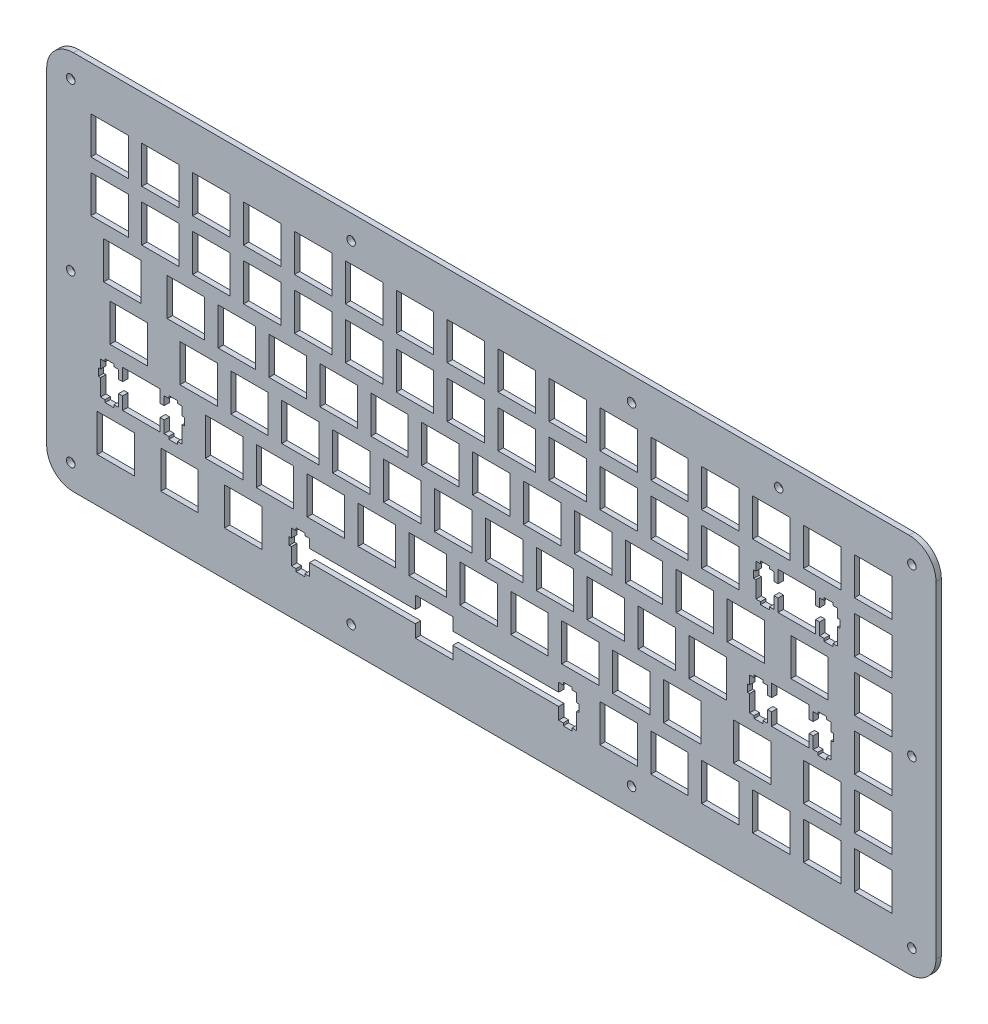
SolidWorks part; units mm, degrees
ref_plane "前视基准面" through (0, 0, 0) normal (0, 0, 1) x (1, 0, 0)
ref_plane "上视基准面" through (0, 0, 0) normal (0, 1, 0) x (1, 0, 0)
ref_plane "右视基准面" through (0, 0, 0) normal (1, 0, 0) x (0, 0, -1)
sketch "草图1" plane through (0, 0, 0) normal (0, 0, 1) x (1, 0, 0)
  line L0 (-71.9647, 54.2413) -> (-57.9647, 54.2413)
  line L1 (-172.8986, 61.7663) -> (147.9033, 61.7663) construction
  line L2 (-172.8986, 61.7663) -> (-172.8986, -68.5358) construction
  line L3 (-172.8986, -68.5358) -> (147.9033, -68.5358) construction
  line L4 (147.9033, 61.7663) -> (147.9033, -68.5358) construction
  line L5 (-165.3745, 54.2413) -> (140.3763, 54.2413) construction
  line L6 (-165.3745, 54.2413) -> (-165.3745, -61.009) construction
  line L7 (-165.3745, -61.009) -> (140.3763, -61.009) construction
  line L8 (140.3763, 54.2413) -> (140.3763, -61.009) construction
  line L9 (32.9683, 54.2413) -> (46.9683, 54.2413)
  line L10 (-165.3745, 3.6152) -> (-165.3745, -10.3848)
  line L11 (-71.9647, -61.009) -> (-57.9647, -61.009)
  line L12 (32.9683, -61.009) -> (46.9683, -61.009)
  line L13 (140.3763, 3.6152) -> (140.3763, -10.3848)
  line L14 (135.9033, 59.7663) -> (135.9033, 56.2413)
  line L15 (142.3763, 49.7663) -> (145.9033, 49.7663)
  line L16 (142.3763, -56.5358) -> (145.9033, -56.5358)
  line L17 (135.9033, -63.009) -> (135.9033, -66.5358)
  line L18 (-160.8986, -63.009) -> (-160.8986, -66.5358)
  line L19 (-167.3745, -56.5358) -> (-170.8986, -56.5358)
  line L20 (-160.8986, 56.2413) -> (-160.8986, 59.7663)
  line L21 (-167.3745, 49.7663) -> (-170.8986, 49.7663)
  line L22 (-73.9647, 56.2413) -> (-73.9647, 59.7663)
  line L23 (-55.9647, 56.2413) -> (-55.9647, 59.7663)
  line L24 (30.9683, 56.2413) -> (30.9683, 59.7663)
  line L25 (48.9683, 56.2413) -> (48.9683, 59.7663)
  line L26 (142.3763, 5.6152) -> (145.9033, 5.6152)
  line L27 (142.3763, -12.3848) -> (145.9033, -12.3848)
  line L28 (48.9683, -63.009) -> (48.9683, -66.5358)
  line L29 (30.9683, -63.009) -> (30.9683, -66.5358)
  line L30 (-55.9647, -63.009) -> (-55.9647, -66.5358)
  line L31 (-73.9647, -63.009) -> (-73.9647, -66.5358)
  line L32 (-167.3745, 5.6152) -> (-170.8986, 5.6152)
  line L33 (-167.3745, -12.3848) -> (-170.8986, -12.3848)
  line L34 (-158.8986, 61.7663) -> (-75.9647, 61.7663)
  line L35 (-53.9647, 61.7663) -> (28.9683, 61.7663)
  line L36 (147.9033, 47.7663) -> (147.9033, 7.6152)
  line L37 (147.9033, -14.3848) -> (147.9033, -54.5358)
  line L38 (133.9033, -68.5358) -> (50.9683, -68.5358)
  line L39 (28.9683, -68.5358) -> (-53.9647, -68.5358)
  line L40 (-75.9647, -68.5358) -> (-158.8986, -68.5358)
  line L41 (-172.8986, -54.5358) -> (-172.8986, -14.3848)
  line L42 (-172.8986, 7.6152) -> (-172.8986, 47.7663)
  line L43 (-165.3745, 51.7663) -> (-165.3745, 52.2413)
  line L44 (-163.3745, 54.2413) -> (-162.8986, 54.2413)
  line L45 (137.9033, 54.2413) -> (138.3763, 54.2413)
  line L46 (140.3763, 52.2413) -> (140.3763, 51.7663)
  line L47 (140.3763, -58.5358) -> (140.3763, -59.009)
  line L48 (138.3763, -61.009) -> (137.9033, -61.009)
  line L49 (-165.3745, -58.5358) -> (-165.3745, -59.009)
  line L50 (-163.3745, -61.009) -> (-162.8986, -61.009)
  line L51 (88.0363, 54.2413) -> (102.0363, 54.2413)
  line L52 (104.0363, 56.2413) -> (104.0363, 59.7663)
  line L53 (106.0363, 61.7663) -> (133.9033, 61.7663)
  line L54 (86.0363, 56.2413) -> (86.0363, 59.7663)
  line L55 (84.0363, 61.7663) -> (50.9683, 61.7663)
  line L56 (-168.8986, 67.7663) -> (143.9033, 67.7663)
  line L57 (153.9033, 57.7663) -> (153.9033, -64.5358)
  line L58 (143.9033, -74.5358) -> (-168.8986, -74.5358)
  line L59 (-178.8986, 57.7663) -> (-178.8986, -64.5358)
  line L60 (-40.9307, -44.0081) -> (-40.9307, -48.71)
  line L61 (-40.9307, -48.71) -> (-80.555, -48.71)
  line L62 (-80.555, -48.71) -> (-80.555, -45.4784)
  line L63 (-80.555, -45.4784) -> (-82.2801, -45.4784)
  line L64 (-82.2801, -45.4784) -> (-82.2801, -44.5579)
  line L65 (-82.2801, -44.5579) -> (-85.5807, -44.5579)
  line L66 (-85.5807, -44.5579) -> (-85.5807, -45.4784)
  line L67 (-85.5807, -45.4784) -> (-87.3047, -45.4784)
  line L68 (-87.3047, -45.4784) -> (-87.3047, -48.71)
  line L69 (-87.3047, -48.71) -> (-88.1298, -48.71)
  line L70 (-88.1298, -48.71) -> (-88.1298, -51.5088)
  line L71 (-88.1298, -51.5088) -> (-87.3047, -51.5088)
  line L72 (-87.3047, -51.5088) -> (-87.3047, -57.7788)
  line L73 (-87.3047, -57.7788) -> (-85.5807, -57.7788)
  line L74 (-85.5807, -57.7788) -> (-85.5807, -58.7587)
  line L75 (-85.5807, -58.7587) -> (-82.2801, -58.7587)
  line L76 (-82.2801, -58.7587) -> (-82.2801, -57.7788)
  line L77 (-82.2801, -57.7788) -> (-80.555, -57.7788)
  line L78 (-80.555, -57.7788) -> (-80.555, -53.3084)
  line L79 (-80.555, -53.3084) -> (-40.9307, -53.3084)
  line L80 (-40.9307, -53.3084) -> (-40.9307, -58.009)
  line L81 (-40.9307, -58.009) -> (-26.9297, -58.009)
  line L82 (-26.9297, -58.009) -> (-26.9297, -53.3084)
  line L83 (-26.9297, -53.3084) -> (12.6943, -53.3084)
  line L84 (12.6943, -53.3084) -> (12.6943, -57.7788)
  line L85 (12.6943, -57.7788) -> (14.4193, -57.7788)
  line L86 (14.4193, -57.7788) -> (14.4193, -58.7587)
  line L87 (14.4193, -58.7587) -> (17.7193, -58.7587)
  line L88 (17.7193, -58.7587) -> (17.7193, -57.7788)
  line L89 (17.7193, -57.7788) -> (19.4453, -57.7788)
  line L90 (19.4453, -57.7788) -> (19.4453, -51.5088)
  line L91 (19.4453, -51.5088) -> (20.2693, -51.5088)
  line L92 (20.2693, -51.5088) -> (20.2693, -48.71)
  line L93 (20.2693, -48.71) -> (19.4453, -48.71)
  line L94 (19.4453, -48.71) -> (19.4453, -45.4784)
  line L95 (19.4453, -45.4784) -> (17.7193, -45.4784)
  line L96 (17.7193, -45.4784) -> (17.7193, -44.5579)
  line L97 (17.7193, -44.5579) -> (14.4193, -44.5579)
  line L98 (14.4193, -44.5579) -> (14.4193, -45.4784)
  line L99 (14.4193, -45.4784) -> (12.6943, -45.4784)
  line L100 (12.6943, -45.4784) -> (12.6943, -48.71)
  line L101 (12.6943, -48.71) -> (-26.9297, -48.71)
  line L102 (-26.9297, -48.71) -> (-26.9297, -44.0081)
  line L103 (-26.9297, -44.0081) -> (-40.9307, -44.0081)
  line L104 (123.3763, -44.0081) -> (137.3763, -44.0081)
  line L105 (137.3763, -44.0081) -> (137.3763, -58.009)
  line L106 (137.3763, -58.009) -> (123.3763, -58.009)
  line L107 (123.3763, -58.009) -> (123.3763, -44.0081)
  line L108 (104.3263, -44.0081) -> (118.3263, -44.0081)
  line L109 (118.3263, -44.0081) -> (118.3263, -58.009)
  line L110 (118.3263, -58.009) -> (104.3263, -58.009)
  line L111 (104.3263, -58.009) -> (104.3263, -44.0081)
  line L112 (85.2763, -44.0081) -> (99.2763, -44.0081)
  line L113 (99.2763, -44.0081) -> (99.2763, -58.009)
  line L114 (99.2763, -58.009) -> (85.2763, -58.009)
  line L115 (85.2763, -58.009) -> (85.2763, -44.0081)
  line L116 (66.2263, -44.0081) -> (80.2263, -44.0081)
  line L117 (80.2263, -44.0081) -> (80.2263, -58.009)
  line L118 (80.2263, -58.009) -> (66.2263, -58.009)
  line L119 (66.2263, -58.009) -> (66.2263, -44.0081)
  line L120 (47.1763, -44.0081) -> (61.1763, -44.0081)
  line L121 (61.1763, -44.0081) -> (61.1763, -58.009)
  line L122 (61.1763, -58.009) -> (47.1763, -58.009)
  line L123 (47.1763, -58.009) -> (47.1763, -44.0081)
  line L124 (28.1263, -44.0081) -> (42.1263, -44.0081)
  line L125 (42.1263, -44.0081) -> (42.1263, -58.009)
  line L126 (42.1263, -58.009) -> (28.1263, -58.009)
  line L127 (28.1263, -58.009) -> (28.1263, -44.0081)
  line L128 (-112.3671, -44.0081) -> (-98.3674, -44.0081)
  line L129 (-98.3674, -44.0081) -> (-98.3674, -58.009)
  line L130 (-98.3674, -58.009) -> (-112.3671, -58.009)
  line L131 (-112.3671, -58.009) -> (-112.3671, -44.0081)
  line L132 (-136.1806, -44.0081) -> (-122.1799, -44.0081)
  line L133 (-122.1799, -44.0081) -> (-122.1799, -58.009)
  line L134 (-122.1799, -58.009) -> (-136.1806, -58.009)
  line L135 (-136.1806, -58.009) -> (-136.1806, -44.0081)
  line L136 (-159.9919, -44.0081) -> (-145.9924, -44.0081)
  line L137 (-145.9924, -44.0081) -> (-145.9924, -58.009)
  line L138 (-145.9924, -58.009) -> (-159.9919, -58.009)
  line L139 (-159.9919, -58.009) -> (-159.9919, -44.0081)
  line L140 (-150.4669, -24.9593) -> (-150.4669, -29.6601)
  line L141 (-150.4669, -29.6601) -> (-151.9924, -29.6601)
  line L142 (-151.9924, -29.6601) -> (-151.9924, -26.4297)
  line L143 (-151.9924, -26.4297) -> (-153.7177, -26.4297)
  line L144 (-153.7177, -26.4297) -> (-153.7177, -25.5079)
  line L145 (-153.7177, -25.5079) -> (-157.0167, -25.5079)
  line L146 (-157.0167, -25.5079) -> (-157.0167, -26.4297)
  line L147 (-157.0167, -26.4297) -> (-158.742, -26.4297)
  line L148 (-158.742, -26.4297) -> (-158.742, -29.6601)
  line L149 (-158.742, -29.6601) -> (-159.5675, -29.6601)
  line L150 (-159.5675, -29.6601) -> (-159.5675, -32.4586)
  line L151 (-159.5675, -32.4586) -> (-158.742, -32.4586)
  line L152 (-158.742, -32.4586) -> (-158.742, -38.7288)
  line L153 (-158.742, -38.7288) -> (-157.0167, -38.7288)
  line L154 (-157.0167, -38.7288) -> (-157.0167, -39.71)
  line L155 (-157.0167, -39.71) -> (-153.7177, -39.71)
  line L156 (-153.7177, -39.71) -> (-153.7177, -38.7288)
  line L157 (-153.7177, -38.7288) -> (-151.9924, -38.7288)
  line L158 (-151.9924, -38.7288) -> (-151.9924, -34.2584)
  line L159 (-151.9924, -34.2584) -> (-150.4669, -34.2584)
  line L160 (-150.4669, -34.2584) -> (-150.4669, -38.959)
  line L161 (-150.4669, -38.959) -> (-136.4674, -38.959)
  line L162 (-136.4674, -38.959) -> (-136.4674, -34.2584)
  line L163 (-136.4674, -34.2584) -> (-134.942, -34.2584)
  line L164 (-134.942, -34.2584) -> (-134.942, -38.7288)
  line L165 (-134.942, -38.7288) -> (-133.2166, -38.7288)
  line L166 (-133.2166, -38.7288) -> (-133.2166, -39.71)
  line L167 (-133.2166, -39.71) -> (-129.9178, -39.71)
  line L168 (-129.9178, -39.71) -> (-129.9178, -38.7288)
  line L169 (-129.9178, -38.7288) -> (-128.1923, -38.7288)
  line L170 (-128.1923, -38.7288) -> (-128.1923, -32.4586)
  line L171 (-128.1923, -32.4586) -> (-127.3668, -32.4586)
  line L172 (-127.3668, -32.4586) -> (-127.3668, -29.6601)
  line L173 (-127.3668, -29.6601) -> (-128.1923, -29.6601)
  line L174 (-128.1923, -29.6601) -> (-128.1923, -26.4297)
  line L175 (-128.1923, -26.4297) -> (-129.9178, -26.4297)
  line L176 (-129.9178, -26.4297) -> (-129.9178, -25.5079)
  line L177 (-129.9178, -25.5079) -> (-133.2166, -25.5079)
  line L178 (-133.2166, -25.5079) -> (-133.2166, -26.4297)
  line L179 (-133.2166, -26.4297) -> (-134.942, -26.4297)
  line L180 (-134.942, -26.4297) -> (-134.942, -29.6601)
  line L181 (-134.942, -29.6601) -> (-136.4674, -29.6601)
  line L182 (-136.4674, -29.6601) -> (-136.4674, -24.9593)
  line L183 (-136.4674, -24.9593) -> (-150.4669, -24.9593)
  line L184 (123.3763, -24.9593) -> (137.3763, -24.9593)
  line L185 (137.3763, -24.9593) -> (137.3763, -38.959)
  line L186 (137.3763, -38.959) -> (123.3763, -38.959)
  line L187 (123.3763, -38.959) -> (123.3763, -24.9593)
  line L188 (104.3263, -24.9593) -> (118.3263, -24.9593)
  line L189 (118.3263, -24.9593) -> (118.3263, -38.959)
  line L190 (118.3263, -38.959) -> (104.3263, -38.959)
  line L191 (104.3263, -38.959) -> (104.3263, -24.9593)
  line L192 (78.1333, -24.9593) -> (92.1323, -24.9593)
  line L193 (92.1323, -24.9593) -> (92.1323, -38.959)
  line L194 (92.1323, -38.959) -> (78.1333, -38.959)
  line L195 (78.1333, -38.959) -> (78.1333, -24.9593)
  line L196 (51.9393, -24.9593) -> (65.9393, -24.9593)
  line L197 (65.9393, -24.9593) -> (65.9393, -38.959)
  line L198 (65.9393, -38.959) -> (51.9393, -38.959)
  line L199 (51.9393, -38.959) -> (51.9393, -24.9593)
  line L200 (32.8893, -24.9593) -> (46.8893, -24.9593)
  line L201 (46.8893, -24.9593) -> (46.8893, -38.959)
  line L202 (46.8893, -38.959) -> (32.8893, -38.959)
  line L203 (32.8893, -38.959) -> (32.8893, -24.9593)
  line L204 (13.8393, -24.9593) -> (27.8393, -24.9593)
  line L205 (27.8393, -24.9593) -> (27.8393, -38.959)
  line L206 (27.8393, -38.959) -> (13.8393, -38.959)
  line L207 (13.8393, -38.959) -> (13.8393, -24.9593)
  line L208 (-5.2107, -24.9593) -> (8.7893, -24.9593)
  line L209 (8.7893, -24.9593) -> (8.7893, -38.959)
  line L210 (8.7893, -38.959) -> (-5.2107, -38.959)
  line L211 (-5.2107, -38.959) -> (-5.2107, -24.9593)
  line L212 (-24.2607, -24.9593) -> (-10.2607, -24.9593)
  line L213 (-10.2607, -24.9593) -> (-10.2607, -38.959)
  line L214 (-10.2607, -38.959) -> (-24.2607, -38.959)
  line L215 (-24.2607, -38.959) -> (-24.2607, -24.9593)
  line L216 (-43.3107, -24.9593) -> (-29.3107, -24.9593)
  line L217 (-29.3107, -24.9593) -> (-29.3107, -38.959)
  line L218 (-29.3107, -38.959) -> (-43.3107, -38.959)
  line L219 (-43.3107, -38.959) -> (-43.3107, -24.9593)
  line L220 (-62.3607, -24.9593) -> (-48.3607, -24.9593)
  line L221 (-48.3607, -24.9593) -> (-48.3607, -38.959)
  line L222 (-48.3607, -38.959) -> (-62.3607, -38.959)
  line L223 (-62.3607, -38.959) -> (-62.3607, -24.9593)
  line L224 (-81.4108, -24.9593) -> (-67.4107, -24.9593)
  line L225 (-67.4107, -24.9593) -> (-67.4107, -38.959)
  line L226 (-67.4107, -38.959) -> (-81.4108, -38.959)
  line L227 (-81.4108, -38.959) -> (-81.4108, -24.9593)
  line L228 (-100.4608, -24.9593) -> (-86.4612, -24.9593)
  line L229 (-86.4612, -24.9593) -> (-86.4612, -38.959)
  line L230 (-86.4612, -38.959) -> (-100.4608, -38.959)
  line L231 (-100.4608, -38.959) -> (-100.4608, -24.9593)
  line L232 (-119.5108, -24.9593) -> (-105.5112, -24.9593)
  line L233 (-105.5112, -24.9593) -> (-105.5112, -38.959)
  line L234 (-105.5112, -38.959) -> (-119.5108, -38.959)
  line L235 (-119.5108, -38.959) -> (-119.5108, -24.9593)
  line L236 (92.4193, -5.9093) -> (92.4193, -10.6101)
  line L237 (92.4193, -10.6101) -> (90.8953, -10.6101)
  line L238 (90.8953, -10.6101) -> (90.8953, -7.3797)
  line L239 (90.8953, -7.3797) -> (89.1703, -7.3797)
  line L240 (89.1703, -7.3797) -> (89.1703, -6.4593)
  line L241 (89.1703, -6.4593) -> (85.8693, -6.4593)
  line L242 (85.8693, -6.4593) -> (85.8693, -7.3797)
  line L243 (85.8693, -7.3797) -> (84.1453, -7.3797)
  line L244 (84.1453, -7.3797) -> (84.1453, -10.6101)
  line L245 (84.1453, -10.6101) -> (83.3203, -10.6101)
  line L246 (83.3203, -10.6101) -> (83.3203, -13.4086)
  line L247 (83.3203, -13.4086) -> (84.1453, -13.4086)
  line L248 (84.1453, -13.4086) -> (84.1453, -19.6789)
  line L249 (84.1453, -19.6789) -> (85.8693, -19.6789)
  line L250 (85.8693, -19.6789) -> (85.8693, -20.66)
  line L251 (85.8693, -20.66) -> (89.1703, -20.66)
  line L252 (89.1703, -20.66) -> (89.1703, -19.6789)
  line L253 (89.1703, -19.6789) -> (90.8953, -19.6789)
  line L254 (90.8953, -19.6789) -> (90.8953, -15.2099)
  line L255 (90.8953, -15.2099) -> (92.4193, -15.2099)
  line L256 (92.4193, -15.2099) -> (92.4193, -19.9089)
  line L257 (92.4193, -19.9089) -> (106.4203, -19.9089)
  line L258 (106.4203, -19.9089) -> (106.4203, -15.2099)
  line L259 (106.4203, -15.2099) -> (107.9443, -15.2099)
  line L260 (107.9443, -15.2099) -> (107.9443, -19.6789)
  line L261 (107.9443, -19.6789) -> (109.6693, -19.6789)
  line L262 (109.6693, -19.6789) -> (109.6693, -20.66)
  line L263 (109.6693, -20.66) -> (112.9693, -20.66)
  line L264 (112.9693, -20.66) -> (112.9693, -19.6789)
  line L265 (112.9693, -19.6789) -> (114.6953, -19.6789)
  line L266 (114.6953, -19.6789) -> (114.6953, -13.4086)
  line L267 (114.6953, -13.4086) -> (115.5193, -13.4086)
  line L268 (115.5193, -13.4086) -> (115.5193, -10.6101)
  line L269 (115.5193, -10.6101) -> (114.6953, -10.6101)
  line L270 (114.6953, -10.6101) -> (114.6953, -7.3797)
  line L271 (114.6953, -7.3797) -> (112.9693, -7.3797)
  line L272 (112.9693, -7.3797) -> (112.9693, -6.4593)
  line L273 (112.9693, -6.4593) -> (109.6693, -6.4593)
  line L274 (109.6693, -6.4593) -> (109.6693, -7.3797)
  line L275 (109.6693, -7.3797) -> (107.9443, -7.3797)
  line L276 (107.9443, -7.3797) -> (107.9443, -10.6101)
  line L277 (107.9443, -10.6101) -> (106.4203, -10.6101)
  line L278 (106.4203, -10.6101) -> (106.4203, -5.9093)
  line L279 (106.4203, -5.9093) -> (92.4193, -5.9093)
  line L280 (123.3763, -5.9093) -> (137.3763, -5.9093)
  line L281 (137.3763, -5.9093) -> (137.3763, -19.9089)
  line L282 (137.3763, -19.9089) -> (123.3763, -19.9089)
  line L283 (123.3763, -19.9089) -> (123.3763, -5.9093)
  line L284 (61.4643, -5.9093) -> (75.4643, -5.9093)
  line L285 (75.4643, -5.9093) -> (75.4643, -19.9089)
  line L286 (75.4643, -19.9089) -> (61.4643, -19.9089)
  line L287 (61.4643, -19.9089) -> (61.4643, -5.9093)
  line L288 (42.4143, -5.9093) -> (56.4143, -5.9093)
  line L289 (56.4143, -5.9093) -> (56.4143, -19.9089)
  line L290 (56.4143, -19.9089) -> (42.4143, -19.9089)
  line L291 (42.4143, -19.9089) -> (42.4143, -5.9093)
  line L292 (23.3643, -5.9093) -> (37.3643, -5.9093)
  line L293 (37.3643, -5.9093) -> (37.3643, -19.9089)
  line L294 (37.3643, -19.9089) -> (23.3643, -19.9089)
  line L295 (23.3643, -19.9089) -> (23.3643, -5.9093)
  line L296 (4.3143, -5.9093) -> (18.3143, -5.9093)
  line L297 (18.3143, -5.9093) -> (18.3143, -19.9089)
  line L298 (18.3143, -19.9089) -> (4.3143, -19.9089)
  line L299 (4.3143, -19.9089) -> (4.3143, -5.9093)
  line L300 (-14.7357, -5.9093) -> (-0.7357, -5.9093)
  line L301 (-0.7357, -5.9093) -> (-0.7357, -19.9089)
  line L302 (-0.7357, -19.9089) -> (-14.7357, -19.9089)
  line L303 (-14.7357, -19.9089) -> (-14.7357, -5.9093)
  line L304 (-33.7857, -5.9093) -> (-19.7857, -5.9093)
  line L305 (-19.7857, -5.9093) -> (-19.7857, -19.9089)
  line L306 (-19.7857, -19.9089) -> (-33.7857, -19.9089)
  line L307 (-33.7857, -19.9089) -> (-33.7857, -5.9093)
  line L308 (-52.8357, -5.9093) -> (-38.8357, -5.9093)
  line L309 (-38.8357, -5.9093) -> (-38.8357, -19.9089)
  line L310 (-38.8357, -19.9089) -> (-52.8357, -19.9089)
  line L311 (-52.8357, -19.9089) -> (-52.8357, -5.9093)
  line L312 (-71.8857, -5.9093) -> (-57.8857, -5.9093)
  line L313 (-57.8857, -5.9093) -> (-57.8857, -19.9089)
  line L314 (-57.8857, -19.9089) -> (-71.8857, -19.9089)
  line L315 (-71.8857, -19.9089) -> (-71.8857, -5.9093)
  line L316 (-90.9358, -5.9093) -> (-76.9362, -5.9093)
  line L317 (-76.9362, -5.9093) -> (-76.9362, -19.9089)
  line L318 (-76.9362, -19.9089) -> (-90.9358, -19.9089)
  line L319 (-90.9358, -19.9089) -> (-90.9358, -5.9093)
  line L320 (-109.9858, -5.9093) -> (-95.9862, -5.9093)
  line L321 (-95.9862, -5.9093) -> (-95.9862, -19.9089)
  line L322 (-95.9862, -19.9089) -> (-109.9858, -19.9089)
  line L323 (-109.9858, -19.9089) -> (-109.9858, -5.9093)
  line L324 (-129.0358, -5.9093) -> (-115.0362, -5.9093)
  line L325 (-115.0362, -5.9093) -> (-115.0362, -19.9089)
  line L326 (-115.0362, -19.9089) -> (-129.0358, -19.9089)
  line L327 (-129.0358, -19.9089) -> (-129.0358, -5.9093)
  line L328 (-155.2308, -5.9093) -> (-141.2299, -5.9093)
  line L329 (-141.2299, -5.9093) -> (-141.2299, -19.9089)
  line L330 (-141.2299, -19.9089) -> (-155.2308, -19.9089)
  line L331 (-155.2308, -19.9089) -> (-155.2308, -5.9093)
  line L332 (123.3763, 13.1407) -> (137.3763, 13.1407)
  line L333 (137.3763, 13.1407) -> (137.3763, -0.8589)
  line L334 (137.3763, -0.8589) -> (123.3763, -0.8589)
  line L335 (123.3763, -0.8589) -> (123.3763, 13.1407)
  line L336 (99.5643, 13.1407) -> (113.5643, 13.1407)
  line L337 (113.5643, 13.1407) -> (113.5643, -0.8589)
  line L338 (113.5643, -0.8589) -> (99.5643, -0.8589)
  line L339 (99.5643, -0.8589) -> (99.5643, 13.1407)
  line L340 (75.7513, 13.1407) -> (89.7513, 13.1407)
  line L341 (89.7513, 13.1407) -> (89.7513, -0.8589)
  line L342 (89.7513, -0.8589) -> (75.7513, -0.8589)
  line L343 (75.7513, -0.8589) -> (75.7513, 13.1407)
  line L344 (56.7013, 13.1407) -> (70.7013, 13.1407)
  line L345 (70.7013, 13.1407) -> (70.7013, -0.8589)
  line L346 (70.7013, -0.8589) -> (56.7013, -0.8589)
  line L347 (56.7013, -0.8589) -> (56.7013, 13.1407)
  line L348 (37.6513, 13.1407) -> (51.6513, 13.1407)
  line L349 (51.6513, 13.1407) -> (51.6513, -0.8589)
  line L350 (51.6513, -0.8589) -> (37.6513, -0.8589)
  line L351 (37.6513, -0.8589) -> (37.6513, 13.1407)
  line L352 (18.6013, 13.1407) -> (32.6013, 13.1407)
  line L353 (32.6013, 13.1407) -> (32.6013, -0.8589)
  line L354 (32.6013, -0.8589) -> (18.6013, -0.8589)
  line L355 (18.6013, -0.8589) -> (18.6013, 13.1407)
  line L356 (-0.4487, 13.1407) -> (13.5513, 13.1407)
  line L357 (13.5513, 13.1407) -> (13.5513, -0.8589)
  line L358 (13.5513, -0.8589) -> (-0.4487, -0.8589)
  line L359 (-0.4487, -0.8589) -> (-0.4487, 13.1407)
  line L360 (-19.4987, 13.1407) -> (-5.4987, 13.1407)
  line L361 (-5.4987, 13.1407) -> (-5.4987, -0.8589)
  line L362 (-5.4987, -0.8589) -> (-19.4987, -0.8589)
  line L363 (-19.4987, -0.8589) -> (-19.4987, 13.1407)
  line L364 (-38.5487, 13.1407) -> (-24.5487, 13.1407)
  line L365 (-24.5487, 13.1407) -> (-24.5487, -0.8589)
  line L366 (-24.5487, -0.8589) -> (-38.5487, -0.8589)
  line L367 (-38.5487, -0.8589) -> (-38.5487, 13.1407)
  line L368 (-57.5987, 13.1407) -> (-43.5987, 13.1407)
  line L369 (-43.5987, 13.1407) -> (-43.5987, -0.8589)
  line L370 (-43.5987, -0.8589) -> (-57.5987, -0.8589)
  line L371 (-57.5987, -0.8589) -> (-57.5987, 13.1407)
  line L372 (-76.6483, 13.1407) -> (-62.6487, 13.1407)
  line L373 (-62.6487, 13.1407) -> (-62.6487, -0.8589)
  line L374 (-62.6487, -0.8589) -> (-76.6483, -0.8589)
  line L375 (-76.6483, -0.8589) -> (-76.6483, 13.1407)
  line L376 (-95.6983, 13.1407) -> (-81.6987, 13.1407)
  line L377 (-81.6987, 13.1407) -> (-81.6987, -0.8589)
  line L378 (-81.6987, -0.8589) -> (-95.6983, -0.8589)
  line L379 (-95.6983, -0.8589) -> (-95.6983, 13.1407)
  line L380 (-114.7483, 13.1407) -> (-100.7487, 13.1407)
  line L381 (-100.7487, 13.1407) -> (-100.7487, -0.8589)
  line L382 (-100.7487, -0.8589) -> (-114.7483, -0.8589)
  line L383 (-114.7483, -0.8589) -> (-114.7483, 13.1407)
  line L384 (-133.7983, 13.1407) -> (-119.7987, 13.1407)
  line L385 (-119.7987, 13.1407) -> (-119.7987, -0.8589)
  line L386 (-119.7987, -0.8589) -> (-133.7983, -0.8589)
  line L387 (-133.7983, -0.8589) -> (-133.7983, 13.1407)
  line L388 (-157.6106, 13.1407) -> (-143.6112, 13.1407)
  line L389 (-143.6112, 13.1407) -> (-143.6112, -0.8589)
  line L390 (-143.6112, -0.8589) -> (-157.6106, -0.8589)
  line L391 (-157.6106, -0.8589) -> (-157.6106, 13.1407)
  line L392 (94.8013, 32.1903) -> (94.8013, 27.4899)
  line L393 (94.8013, 27.4899) -> (93.2763, 27.4899)
  line L394 (93.2763, 27.4899) -> (93.2763, 30.7203)
  line L395 (93.2763, 30.7203) -> (91.5523, 30.7203)
  line L396 (91.5523, 30.7203) -> (91.5523, 31.6403)
  line L397 (91.5523, 31.6403) -> (88.2523, 31.6403)
  line L398 (88.2523, 31.6403) -> (88.2523, 30.7203)
  line L399 (88.2523, 30.7203) -> (86.5263, 30.7203)
  line L400 (86.5263, 30.7203) -> (86.5263, 27.4899)
  line L401 (86.5263, 27.4899) -> (85.7013, 27.4899)
  line L402 (85.7013, 27.4899) -> (85.7013, 24.6914)
  line L403 (85.7013, 24.6914) -> (86.5263, 24.6914)
  line L404 (86.5263, 24.6914) -> (86.5263, 18.4211)
  line L405 (86.5263, 18.4211) -> (88.2523, 18.4211)
  line L406 (88.2523, 18.4211) -> (88.2523, 17.44)
  line L407 (88.2523, 17.44) -> (91.5523, 17.44)
  line L408 (91.5523, 17.44) -> (91.5523, 18.4211)
  line L409 (91.5523, 18.4211) -> (93.2763, 18.4211)
  line L410 (93.2763, 18.4211) -> (93.2763, 22.8901)
  line L411 (93.2763, 22.8901) -> (94.8013, 22.8901)
  line L412 (94.8013, 22.8901) -> (94.8013, 18.1911)
  line L413 (94.8013, 18.1911) -> (108.8013, 18.1911)
  line L414 (108.8013, 18.1911) -> (108.8013, 22.8901)
  line L415 (108.8013, 22.8901) -> (110.3263, 22.8901)
  line L416 (110.3263, 22.8901) -> (110.3263, 18.4211)
  line L417 (110.3263, 18.4211) -> (112.0523, 18.4211)
  line L418 (112.0523, 18.4211) -> (112.0523, 17.44)
  line L419 (112.0523, 17.44) -> (115.3513, 17.44)
  line L420 (115.3513, 17.44) -> (115.3513, 18.4211)
  line L421 (115.3513, 18.4211) -> (117.0763, 18.4211)
  line L422 (117.0763, 18.4211) -> (117.0763, 24.6914)
  line L423 (117.0763, 24.6914) -> (117.9023, 24.6914)
  line L424 (117.9023, 24.6914) -> (117.9023, 27.4899)
  line L425 (117.9023, 27.4899) -> (117.0763, 27.4899)
  line L426 (117.0763, 27.4899) -> (117.0763, 30.7203)
  line L427 (117.0763, 30.7203) -> (115.3513, 30.7203)
  line L428 (115.3513, 30.7203) -> (115.3513, 31.6403)
  line L429 (115.3513, 31.6403) -> (112.0523, 31.6403)
  line L430 (112.0523, 31.6403) -> (112.0523, 30.7203)
  line L431 (112.0523, 30.7203) -> (110.3263, 30.7203)
  line L432 (110.3263, 30.7203) -> (110.3263, 27.4899)
  line L433 (110.3263, 27.4899) -> (108.8013, 27.4899)
  line L434 (108.8013, 27.4899) -> (108.8013, 32.1903)
  line L435 (108.8013, 32.1903) -> (94.8013, 32.1903)
  line L436 (123.3763, 32.1903) -> (137.3763, 32.1903)
  line L437 (137.3763, 32.1903) -> (137.3763, 18.1911)
  line L438 (137.3763, 18.1911) -> (123.3763, 18.1911)
  line L439 (123.3763, 18.1911) -> (123.3763, 32.1903)
  line L440 (66.2263, 32.1903) -> (80.2263, 32.1903)
  line L441 (80.2263, 32.1903) -> (80.2263, 18.1911)
  line L442 (80.2263, 18.1911) -> (66.2263, 18.1911)
  line L443 (66.2263, 18.1911) -> (66.2263, 32.1903)
  line L444 (47.1763, 32.1903) -> (61.1763, 32.1903)
  line L445 (61.1763, 32.1903) -> (61.1763, 18.1911)
  line L446 (61.1763, 18.1911) -> (47.1763, 18.1911)
  line L447 (47.1763, 18.1911) -> (47.1763, 32.1903)
  line L448 (28.1263, 32.1903) -> (42.1263, 32.1903)
  line L449 (42.1263, 32.1903) -> (42.1263, 18.1911)
  line L450 (42.1263, 18.1911) -> (28.1263, 18.1911)
  line L451 (28.1263, 18.1911) -> (28.1263, 32.1903)
  line L452 (9.0763, 32.1903) -> (23.0763, 32.1903)
  line L453 (23.0763, 32.1903) -> (23.0763, 18.1911)
  line L454 (23.0763, 18.1911) -> (9.0763, 18.1911)
  line L455 (9.0763, 18.1911) -> (9.0763, 32.1903)
  line L456 (-9.9737, 32.1903) -> (4.0263, 32.1903)
  line L457 (4.0263, 32.1903) -> (4.0263, 18.1911)
  line L458 (4.0263, 18.1911) -> (-9.9737, 18.1911)
  line L459 (-9.9737, 18.1911) -> (-9.9737, 32.1903)
  line L460 (-29.0237, 32.1903) -> (-15.0237, 32.1903)
  line L461 (-15.0237, 32.1903) -> (-15.0237, 18.1911)
  line L462 (-15.0237, 18.1911) -> (-29.0237, 18.1911)
  line L463 (-29.0237, 18.1911) -> (-29.0237, 32.1903)
  line L464 (-48.0747, 32.1903) -> (-34.0737, 32.1903)
  line L465 (-34.0737, 32.1903) -> (-34.0737, 18.1911)
  line L466 (-34.0737, 18.1911) -> (-48.0747, 18.1911)
  line L467 (-48.0747, 18.1911) -> (-48.0747, 32.1903)
  line L468 (-67.1247, 32.1903) -> (-53.1237, 32.1903)
  line L469 (-53.1237, 32.1903) -> (-53.1237, 18.1911)
  line L470 (-53.1237, 18.1911) -> (-67.1247, 18.1911)
  line L471 (-67.1247, 18.1911) -> (-67.1247, 32.1903)
  line L472 (-86.1733, 32.1903) -> (-72.1737, 32.1903)
  line L473 (-72.1737, 32.1903) -> (-72.1737, 18.1911)
  line L474 (-72.1737, 18.1911) -> (-86.1733, 18.1911)
  line L475 (-86.1733, 18.1911) -> (-86.1733, 32.1903)
  line L476 (-105.2233, 32.1903) -> (-91.2237, 32.1903)
  line L477 (-91.2237, 32.1903) -> (-91.2237, 18.1911)
  line L478 (-91.2237, 18.1911) -> (-105.2233, 18.1911)
  line L479 (-105.2233, 18.1911) -> (-105.2233, 32.1903)
  line L480 (-124.2733, 32.1903) -> (-110.2737, 32.1903)
  line L481 (-110.2737, 32.1903) -> (-110.2737, 18.1911)
  line L482 (-110.2737, 18.1911) -> (-124.2733, 18.1911)
  line L483 (-124.2733, 18.1911) -> (-124.2733, 32.1903)
  line L484 (-143.3231, 32.1903) -> (-129.3237, 32.1903)
  line L485 (-129.3237, 32.1903) -> (-129.3237, 18.1911)
  line L486 (-129.3237, 18.1911) -> (-143.3231, 18.1911)
  line L487 (-143.3231, 18.1911) -> (-143.3231, 32.1903)
  line L488 (-162.3745, 32.1903) -> (-148.3737, 32.1903)
  line L489 (-148.3737, 32.1903) -> (-148.3737, 18.1911)
  line L490 (-148.3737, 18.1911) -> (-162.3745, 18.1911)
  line L491 (-162.3745, 18.1911) -> (-162.3745, 32.1903)
  line L492 (123.3763, 51.2413) -> (137.3763, 51.2413)
  line L493 (137.3763, 51.2413) -> (137.3763, 37.2413)
  line L494 (137.3763, 37.2413) -> (123.3763, 37.2413)
  line L495 (123.3763, 37.2413) -> (123.3763, 51.2413)
  line L496 (104.3263, 51.2413) -> (118.3263, 51.2413)
  line L497 (118.3263, 51.2413) -> (118.3263, 37.2413)
  line L498 (118.3263, 37.2413) -> (104.3263, 37.2413)
  line L499 (104.3263, 37.2413) -> (104.3263, 51.2413)
  line L500 (85.2763, 51.2413) -> (99.2763, 51.2413)
  line L501 (99.2763, 51.2413) -> (99.2763, 37.2413)
  line L502 (99.2763, 37.2413) -> (85.2763, 37.2413)
  line L503 (85.2763, 37.2413) -> (85.2763, 51.2413)
  line L504 (66.2263, 51.2413) -> (80.2263, 51.2413)
  line L505 (80.2263, 51.2413) -> (80.2263, 37.2413)
  line L506 (80.2263, 37.2413) -> (66.2263, 37.2413)
  line L507 (66.2263, 37.2413) -> (66.2263, 51.2413)
  line L508 (47.1763, 51.2413) -> (61.1763, 51.2413)
  line L509 (61.1763, 51.2413) -> (61.1763, 37.2413)
  line L510 (61.1763, 37.2413) -> (47.1763, 37.2413)
  line L511 (47.1763, 37.2413) -> (47.1763, 51.2413)
  line L512 (28.1263, 51.2413) -> (42.1263, 51.2413)
  line L513 (42.1263, 51.2413) -> (42.1263, 37.2413)
  line L514 (42.1263, 37.2413) -> (28.1263, 37.2413)
  line L515 (28.1263, 37.2413) -> (28.1263, 51.2413)
  line L516 (9.0763, 51.2413) -> (23.0763, 51.2413)
  line L517 (23.0763, 51.2413) -> (23.0763, 37.2413)
  line L518 (23.0763, 37.2413) -> (9.0763, 37.2413)
  line L519 (9.0763, 37.2413) -> (9.0763, 51.2413)
  line L520 (-9.9737, 51.2413) -> (4.0263, 51.2413)
  line L521 (4.0263, 51.2413) -> (4.0263, 37.2413)
  line L522 (4.0263, 37.2413) -> (-9.9737, 37.2413)
  line L523 (-9.9737, 37.2413) -> (-9.9737, 51.2413)
  line L524 (-29.0237, 51.2413) -> (-15.0237, 51.2413)
  line L525 (-15.0237, 51.2413) -> (-15.0237, 37.2413)
  line L526 (-15.0237, 37.2413) -> (-29.0237, 37.2413)
  line L527 (-29.0237, 37.2413) -> (-29.0237, 51.2413)
  line L528 (-48.0747, 51.2413) -> (-34.0737, 51.2413)
  line L529 (-34.0737, 51.2413) -> (-34.0737, 37.2413)
  line L530 (-34.0737, 37.2413) -> (-48.0747, 37.2413)
  line L531 (-48.0747, 37.2413) -> (-48.0747, 51.2413)
  line L532 (-67.1247, 51.2413) -> (-53.1237, 51.2413)
  line L533 (-53.1237, 51.2413) -> (-53.1237, 37.2413)
  line L534 (-53.1237, 37.2413) -> (-67.1247, 37.2413)
  line L535 (-67.1247, 37.2413) -> (-67.1247, 51.2413)
  line L536 (-86.1733, 51.2413) -> (-72.1737, 51.2413)
  line L537 (-72.1737, 51.2413) -> (-72.1737, 37.2413)
  line L538 (-72.1737, 37.2413) -> (-86.1733, 37.2413)
  line L539 (-86.1733, 37.2413) -> (-86.1733, 51.2413)
  line L540 (-105.2233, 51.2413) -> (-91.2237, 51.2413)
  line L541 (-91.2237, 51.2413) -> (-91.2237, 37.2413)
  line L542 (-91.2237, 37.2413) -> (-105.2233, 37.2413)
  line L543 (-105.2233, 37.2413) -> (-105.2233, 51.2413)
  line L544 (-124.2733, 51.2413) -> (-110.2737, 51.2413)
  line L545 (-110.2737, 51.2413) -> (-110.2737, 37.2413)
  line L546 (-110.2737, 37.2413) -> (-124.2733, 37.2413)
  line L547 (-124.2733, 37.2413) -> (-124.2733, 51.2413)
  line L548 (-143.3231, 51.2413) -> (-129.3237, 51.2413)
  line L549 (-129.3237, 51.2413) -> (-129.3237, 37.2413)
  line L550 (-129.3237, 37.2413) -> (-143.3231, 37.2413)
  line L551 (-143.3231, 37.2413) -> (-143.3231, 51.2413)
  line L552 (-162.3745, 51.2413) -> (-148.3737, 51.2413)
  line L553 (-148.3737, 51.2413) -> (-148.3737, 37.2413)
  line L554 (-148.3737, 37.2413) -> (-162.3745, 37.2413)
  line L555 (-162.3745, 37.2413) -> (-162.3745, 51.2413)
  circle A0 centre (-169.8986, 58.7663) radius 1.6
  circle A1 centre (-64.9647, 58.7663) radius 1.6
  circle A2 centre (39.9683, 58.7663) radius 1.6
  circle A3 centre (144.9033, 58.7663) radius 1.6
  circle A4 centre (144.9033, -3.3848) radius 1.5998
  circle A5 centre (144.9033, -65.5358) radius 1.5999
  circle A6 centre (39.9683, -65.5358) radius 1.5999
  circle A7 centre (-64.9647, -65.5358) radius 1.5999
  circle A8 centre (-169.8986, -65.5358) radius 1.5999
  circle A9 centre (-169.8986, -3.3848) radius 1.5998
  arc A10 (-170.8986, 5.6152) -> (-172.8986, 7.6152) centre (-170.8986, 7.6152) cw
  arc A11 (-165.3745, 3.6152) -> (-167.3745, 5.6152) centre (-167.3745, 3.6152) ccw
  arc A12 (-165.3745, -10.3848) -> (-167.3745, -12.3848) centre (-167.3745, -10.3848) cw
  arc A13 (-170.8986, -12.3848) -> (-172.8986, -14.3848) centre (-170.8986, -14.3848) ccw
  arc A14 (-170.8986, -56.5358) -> (-172.8986, -54.5358) centre (-170.8986, -54.5358) cw
  arc A15 (-167.3745, -56.5358) -> (-165.3745, -58.5358) centre (-167.3745, -58.5358) cw
  arc A16 (-165.3745, -59.009) -> (-163.3745, -61.009) centre (-163.3745, -59.009) ccw
  arc A17 (-160.8986, -63.009) -> (-162.8986, -61.009) centre (-162.8986, -63.009) ccw
  arc A18 (-160.8986, -66.5358) -> (-158.8986, -68.5358) centre (-158.8986, -66.5358) ccw
  arc A19 (-73.9647, -66.5358) -> (-75.9647, -68.5358) centre (-75.9647, -66.5358) cw
  arc A20 (-71.9647, -61.009) -> (-73.9647, -63.009) centre (-71.9647, -63.009) ccw
  arc A21 (-57.9647, -61.009) -> (-55.9647, -63.009) centre (-57.9647, -63.009) cw
  arc A22 (-55.9647, -66.5358) -> (-53.9647, -68.5358) centre (-53.9647, -66.5358) ccw
  arc A23 (30.9683, -66.5358) -> (28.9683, -68.5358) centre (28.9683, -66.5358) cw
  arc A24 (32.9683, -61.009) -> (30.9683, -63.009) centre (32.9683, -63.009) ccw
  arc A25 (46.9683, -61.009) -> (48.9683, -63.009) centre (46.9683, -63.009) cw
  arc A26 (48.9683, -66.5358) -> (50.9683, -68.5358) centre (50.9683, -66.5358) ccw
  arc A27 (135.9033, -66.5358) -> (133.9033, -68.5358) centre (133.9033, -66.5358) cw
  arc A28 (135.9033, -63.009) -> (137.9033, -61.009) centre (137.9033, -63.009) cw
  arc A29 (140.3763, -59.009) -> (138.3763, -61.009) centre (138.3763, -59.009) cw
  arc A30 (142.3763, -56.5358) -> (140.3763, -58.5358) centre (142.3763, -58.5358) ccw
  arc A31 (145.9033, -56.5358) -> (147.9033, -54.5358) centre (145.9033, -54.5358) ccw
  arc A32 (145.9033, -12.3848) -> (147.9033, -14.3848) centre (145.9033, -14.3848) cw
  arc A33 (140.3763, -10.3848) -> (142.3763, -12.3848) centre (142.3763, -10.3848) ccw
  arc A34 (140.3763, 3.6152) -> (142.3763, 5.6152) centre (142.3763, 3.6152) cw
  arc A35 (145.9033, 5.6152) -> (147.9033, 7.6152) centre (145.9033, 7.6152) ccw
  arc A36 (145.9033, 49.7663) -> (147.9033, 47.7663) centre (145.9033, 47.7663) cw
  arc A37 (142.3763, 49.7663) -> (140.3763, 51.7663) centre (142.3763, 51.7663) cw
  arc A38 (140.3763, 52.2413) -> (138.3763, 54.2413) centre (138.3763, 52.2413) ccw
  arc A39 (137.9033, 54.2413) -> (135.9033, 56.2413) centre (137.9033, 56.2413) cw
  arc A40 (135.9033, 59.7663) -> (133.9033, 61.7663) centre (133.9033, 59.7663) ccw
  arc A41 (48.9683, 59.7663) -> (50.9683, 61.7663) centre (50.9683, 59.7663) cw
  arc A42 (48.9683, 56.2413) -> (46.9683, 54.2413) centre (46.9683, 56.2413) cw
  arc A43 (32.9683, 54.2413) -> (30.9683, 56.2413) centre (32.9683, 56.2413) cw
  arc A44 (30.9683, 59.7663) -> (28.9683, 61.7663) centre (28.9683, 59.7663) ccw
  arc A45 (-73.9647, 56.2413) -> (-71.9647, 54.2413) centre (-71.9647, 56.2413) ccw
  arc A46 (-55.9647, 59.7663) -> (-53.9647, 61.7663) centre (-53.9647, 59.7663) cw
  arc A47 (-55.9647, 56.2413) -> (-57.9647, 54.2413) centre (-57.9647, 56.2413) cw
  arc A48 (-73.9647, 59.7663) -> (-75.9647, 61.7663) centre (-75.9647, 59.7663) ccw
  arc A49 (-160.8986, 59.7663) -> (-158.8986, 61.7663) centre (-158.8986, 59.7663) cw
  arc A50 (-160.8986, 56.2413) -> (-162.8986, 54.2413) centre (-162.8986, 56.2413) cw
  arc A51 (-163.3745, 54.2413) -> (-165.3745, 52.2413) centre (-163.3745, 52.2413) ccw
  arc A52 (-165.3745, 51.7663) -> (-167.3745, 49.7663) centre (-167.3745, 51.7663) cw
  arc A53 (-170.8986, 49.7663) -> (-172.8986, 47.7663) centre (-170.8986, 47.7663) ccw
  circle A54 centre (95.0363, 58.7663) radius 1.6
  arc A55 (104.0363, 59.7663) -> (106.0363, 61.7663) centre (106.0363, 59.7663) cw
  arc A56 (102.0363, 54.2413) -> (104.0363, 56.2413) centre (102.0363, 56.2413) ccw
  arc A57 (88.0363, 54.2413) -> (86.0363, 56.2413) centre (88.0363, 56.2413) cw
  arc A58 (84.0363, 61.7663) -> (86.0363, 59.7663) centre (84.0363, 59.7663) cw
  arc A59 (-168.8986, 67.7663) -> (-178.8986, 57.7663) centre (-168.8986, 57.7663) ccw
  arc A60 (-168.8986, -74.5358) -> (-178.8986, -64.5358) centre (-168.8986, -64.5358) cw
  arc A61 (143.9033, -74.5358) -> (153.9033, -64.5358) centre (143.9033, -64.5358) ccw
  arc A62 (153.9033, 57.7663) -> (143.9033, 67.7663) centre (143.9033, 57.7663) ccw
  point P10 (-64.9647, 54.2413)
  point P13 (39.9683, 54.2413)
  point P16 (-165.3745, -3.3848)
  point P19 (-64.9647, -61.009)
  point P22 (39.9683, -61.009)
  point P25 (140.3763, -3.3848)
  point P399 (135.9033, 61.7663)
  point P402 (48.9683, 61.7663)
  point P666 (95.0363, 54.2413)
  dimension "D17" = 2
  dimension "D20" = 2
  dimension "D21" = 10
  dimension "D1" = 6
  dimension "D2" = 6
  dimension "D3" = 6
  dimension "D4" = 6
  dimension "D5" = 3
  dimension "D6" = 3
  dimension "D7" = 3
  dimension "D8" = 3
  dimension "D9" = 9
  dimension "D10" = 9
  dimension "D11" = 9
  dimension "D12" = 9
  dimension "D13" = 9
  dimension "D14" = 9
  dimension "D15" = 9
  dimension "D16" = 9
  dimension "D18" = 6
  dimension "D19" = 55.068
extrude "凸台-拉伸1" add sketch "草图1" along normal blind 2 contours L57 A62 L56 A59 L59 A60 L58 A61 L55 A58 L54 A57 L51 A56 L52 A55 L53 A40 L14 A39 L45 A38 L46 A37 L15 A36 L36 A35 L26 A34 L13 A33 L27 A32 L37 A31 L16 A30 L47 A29 L48 A28 L17 A27 L38 A26 L28 A25 L12 A24 region at (-12.4977, 64.1468, 0)
extrude "凸台-拉伸2" add sketch "草图1<3>" along normal blind 2 contours A58 L55 A41 L25 A42 L9 A43 L24 A44 L35 A46 L23 A47 L0 A45 L22 A48 L34 A49 L20 A50 L44 A51 L43 A52 L21 A53 L42 A10 L32 A11 L10 A12 L33 A13 L41 A14 L19 A15 L49 A16 L50 A17 L18 A18 L40 A19 L31 A20 L11 A21 region at (-14.7199, -5.2926, 0)
sketch "草图1<3>" plane through (0, 0, 0) normal (0, 0, 1) x (1, 0, 0) same geometry as "草图1"
